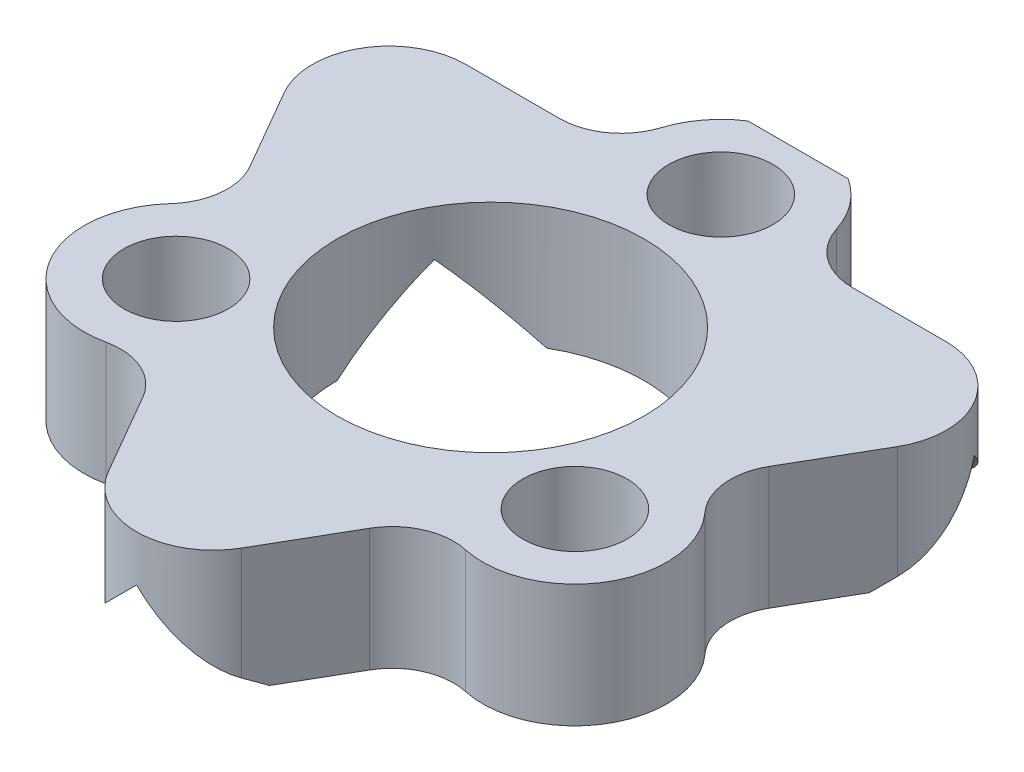
SolidWorks part; units mm, degrees
note: '?' marks a value the reader was unsure of.
material "Chrome Stainless Steel"
ref_plane "Front Plane" through (0, 0, 0) normal (0, 0, 1) x (1, 0, 0)
ref_plane "Top Plane" through (0, 0, 0) normal (0, 1, 0) x (1, 0, 0)
ref_plane "Right Plane" through (0, 0, 0) normal (1, 0, 0) x (0, 0, -1)
sketch "Sketch1" plane through (0, 0, 0) normal (0, 1, 0) x (1, 0, 0)
  line L0 (-9.9899, 3.147) -> (-8.4595, 0.4962)
  line L1 (2.1651, -10.4061) -> (3.6955, -7.7554)
  line L2 (7.8249, 6.897) -> (4.7641, 6.897)
  line L3 (-6.6271, -3.9469) -> (9.3066, 5.2524) construction
  line L4 (0, 6.897) -> (0, -11.9869) construction
  line L5 (4.3301, -2.6207) -> (-9.863, 5.5736) construction
  line L6 (-3.6955, -7.7554) -> (-2.1651, -10.4061)
  line L7 (-12.155, 6.897) -> (-2.961, 6.897) construction
  line L8 (12.155, 6.897) -> (0, -14.1561) construction
  line L9 (0, -14.1561) -> (-12.155, 6.897) construction
  line L10 (-12.155, 6.897) -> (12.155, 6.897) construction
  line L11 (8.4595, 0.4962) -> (9.9899, 3.147)
  line L12 (-4.7641, 6.897) -> (-7.8249, 6.897)
  line L13 (2.961, 6.897) -> (12.155, 6.897) construction
  circle A0 centre (0, -0.1207) radius 5
  circle A1 centre (0, -0.1207) radius 7.5 construction
  arc A2 (-5.8546, -6.8015) -> (-8.713, -1.8505) centre (-6.4952, -3.8707) cw
  arc A3 (-3.6955, -7.7554) -> (-5.8546, -6.8015) centre (-5.4275, -8.7554) ccw
  arc A4 (-9.9899, 3.147) -> (-7.8249, 6.897) centre (-7.8249, 4.397) cw
  arc A5 (2.1651, -10.4061) -> (-2.1651, -10.4061) centre (0, -9.1561) cw
  arc A6 (7.8249, 6.897) -> (9.9899, 3.147) centre (7.8249, 4.397) cw
  arc A7 (-8.4595, 0.4962) -> (-8.713, -1.8505) centre (-10.1916, -0.5038) cw
  arc A8 (3.6955, -7.7554) -> (5.8546, -6.8015) centre (5.4275, -8.7554) cw
  arc A9 (8.713, -1.8505) -> (5.8546, -6.8015) centre (6.4952, -3.8707) cw
  arc A10 (8.713, -1.8505) -> (8.4595, 0.4962) centre (10.1916, -0.5038) cw
  arc A11 (-2.8585, 8.2899) -> (2.8585, 8.2899) centre (0, 7.3793) cw
  arc A12 (-4.7641, 6.897) -> (-2.8585, 8.2899) centre (-4.7641, 8.897) ccw
  arc A13 (4.7641, 6.897) -> (2.8585, 8.2899) centre (4.7641, 8.897) cw
  point P7 (-6.4952, -3.8707)
  point P8 (0, 7.3793)
  point P9 (-12.155, 6.897)
  point P10 (6.4952, -3.8707)
  point P12 (0, -14.1561)
  point P16 (0, -0.1207)
  point P30 (-4.597, -6.1939)
  point P54 (40.5117, -0.4369)
  dimension "D1" = 10
  dimension "D5" = 15
  dimension "D6" = 2.5
  dimension "D7" = 3
  dimension "D8" = 2
  dimension "D9" = 2
  dimension "D10" = 3
  dimension "D11" = 2
  dimension "D12" = 3
  dimension "D2" = 120
  dimension "D3" = 240
  dimension "D4" = 24.31
  dimension "D13" = 0
extrude "Extrude1" add sketch "Sketch1" along normal blind 4
hole_wizard "M3 Clearance Hole1" positions "3DSketch1" profile "Sketch6" hole size "M3" standard "Ansi Metric"
sketch3d "3DSketch1"
  line L0 (-6.4952, 4, 3.8707) -> (-6.4952, 0, 3.8707) construction
  point P0 (-6.4952, 4, 3.8707)
sketch "Sketch6" plane through (-6.4952, 4, 3.8707) normal (1, 0, 0) x (0, 0, 1)
  line L0 (0, 0) -> (0, 11.0215)
  line L1 (0, 11.0215) -> (1.7, 10)
  line L2 (1.7, 10) -> (1.7, 0)
  line L5 (1.7, 0) -> (0, 0)
  line L10 (0, 11.0215) -> (-1.7, 10) construction
  line L11 (0, -6.35) -> (0, 107.95) construction
  dimension "Hole Dia." = 3.4
  dimension "Hole Depth" = 10
  dimension "Drill Angle" = 118
pattern_circular "CirPattern2" count 3 over 360 about axis through (0, 0, 0.1207) along (0, 1, 0) of "M3 Clearance Hole1"
sketch "GrooveSketch" plane through (0, 0, 0) normal (0, 0, 1) x (1, 0, 0)
  line L0 (-2.1651, 4) -> (2.1651, 0) construction
  line L1 (2.1651, 4) -> (-2.1651, 0) construction
  line L2 (0, 0) -> (0, 2.5) construction
  line L3 (-2.1651, 0) -> (2.1651, 0) construction
  line L4 (0, 0) -> (-5.8546, 0) construction
  line L5 (0, 0) -> (5.8546, 0) construction
  line L6 (0, 2.5) -> (-2.5, 0)
  line L7 (0, 2.5) -> (2.5, 0)
  circle A0 centre (0, -0.8658) radius 2.38 construction
  dimension "D2" = 4.76
  dimension "D1" = 2.5
  dimension "D3" = 90
  dimension "D4" = 45
extrude "Extrude4" cut sketch "GrooveSketch" along normal up to next from surface
ref_axis "Axis1" through (0, 4, 0.1207) along (0, -1, 0)?
ref_plane "Plane1" through (0.0523, 0, 0.0302) normal (-0.866, 0, -0.5) x (-0.5, 0, 0.866)
ref_plane "Plane2" through (-0.0523, 0, 0.0302) normal (0.866, 0, -0.5) x (-0.5, 0, -0.866)
sketch "Sketch9" plane through (0.0523, 0, 0.0302) normal (-0.866, 0, -0.5) x (-0.5, 0, 0.866)
  line L2 (0.1046, 0) -> (0.1046, 2.5) construction
  line L3 (0.1046, 0) -> (-8.7995, 0) construction
  line L4 (0.1046, 0) -> (2.9096, 0) construction
  line L5 (0.1046, 2.5) -> (-2.3954, 0)
  line L6 (0.1046, 2.5) -> (2.6046, 0)
  line L7 (0.1046, 4) -> (0.1046, 0) construction
  line L8 (-2.0605, 0) -> (2.2696, 0) construction
  circle A0 centre (0.1046, -0.8658) radius 2.38 construction
  dimension "D1" = 4.76
  dimension "D2" = 2.5
  dimension "D3" = 90
  dimension "D4" = 45
extrude "Extrude5" cut sketch "Sketch9" along normal through all from surface
sketch "Sketch10" plane through (-0.0523, 0, 0.0302) normal (0.866, 0, -0.5) x (-0.5, 0, -0.866)
  line L2 (-0.1046, 0) -> (-0.1046, 2.5) construction
  line L3 (-0.1046, 0) -> (13.4676, 0) construction
  line L4 (-0.1046, 0) -> (25.1768, 0) construction
  line L5 (-0.1046, 2.5) -> (-2.6046, 0)
  line L6 (-0.1046, 2.5) -> (2.3954, 0)
  line L7 (-2.2696, 0) -> (2.0605, 0) construction
  line L8 (-0.1046, 4) -> (-0.1046, 0) construction
  circle A0 centre (-0.1046, -0.8658) radius 2.38 construction
  dimension "D1" = 4.76
  dimension "D2" = 2.5
  dimension "D3" = 90
  dimension "D4" = 45
extrude "Extrude6" cut sketch "Sketch10" along normal through all from surface
sketch "Sketch11" plane through (0, 4, 0) normal (0, 1, 0) x (-1, 0, 0)
  line L0 (4.7641, -6.897) -> (7.8249, -6.897) construction
  line L1 (7.2757, -9.897) -> (-7.6674, -9.897)
  line L2 (7.2757, -9.897) -> (7.2757, -12.0797)
  line L3 (7.2757, -12.0797) -> (-7.6674, -12.0797)
  line L4 (-7.6674, -9.897) -> (-7.6674, -12.0797)
  point P4 (6.2945, -6.897)
  dimension "D1" = 3
extrude "Extrude7" cut sketch "Sketch11" against normal blind 10
sketch "Sketch13" plane through (0, 0, -9.897) normal (0, 0, -1) x (-1, 0, 0)
  line L0 (0, 7.9021) -> (0, -2.2272) construction
  line L1 (0, 4) -> (0, 0) construction
hole_wizard "Ø0.5 (0.5) Diameter Hole1" positions "3DSketch2" profile "Sketch14" hole size "Ø0.5" standard "Ansi Metric"
sketch3d "3DSketch2"
  line L0 (0, 7.9021, -9.897) -> (0, -2.2272, -9.897) construction
  line L1 (-1.6313, 4, -9.897) -> (1.6313, 4, -9.897) construction
  point P0 (0, 2.5, -9.897)
  dimension "D1" = 1.5
sketch "Sketch14" plane through (0, 2.5, -9.897) normal (1, 0, 0) x (0, 1, 0)
  line L0 (0, 0) -> (0, 0.4002)
  line L1 (0, 0.4002) -> (0.25, 0.25)
  line L2 (0.25, 0.25) -> (0.25, 0)
  line L5 (0.25, 0) -> (0, 0)
  line L10 (0, 0.4002) -> (-0.25, 0.25) construction
  line L11 (0, -6.35) -> (0, 107.95) construction
  dimension "Hole Dia." = 0.5
  dimension "Hole Depth" = 0.25
  dimension "Drill Angle" = 118
sketch "Sketch16" plane through (0, 0, -6.897) normal (0, 0, -1) x (-1, 0, 0)
  line L0 (0, -2.4425) -> (0, 8.6057) construction
hole_wizard "Ø0.5 (0.5) Diameter Hole2" positions "3DSketch4" profile "Sketch17" hole size "Ø0.5" standard "Ansi Metric"
sketch3d "3DSketch4"
  line L0 (7.8249, 4, -6.897) -> (4.7641, 4, -6.897) construction
  line L1 (0, -2.4425, -6.897) -> (0, 8.6057, -6.897) construction
  point P0 (6.5, 2.5, -6.897)
  dimension "D1" = 1.5
  dimension "D2" = 6.5
sketch "Sketch17" plane through (6.5, 2.5, -6.897) normal (1, 0, 0) x (0, 1, 0)
  line L0 (0, 0) -> (0, 0.4002)
  line L1 (0, 0.4002) -> (0.25, 0.25)
  line L2 (0.25, 0.25) -> (0.25, 0)
  line L5 (0.25, 0) -> (0, 0)
  line L10 (0, 0.4002) -> (-0.25, 0.25) construction
  line L11 (0, -6.35) -> (0, 107.95) construction
  dimension "Hole Dia." = 0.5
  dimension "Hole Depth" = 0.25
  dimension "Drill Angle" = 118
hole_wizard "Ø0.5 (0.5) Diameter Hole3" positions "3DSketch5" profile "Sketch18" hole size "Ø0.5" standard "Ansi Metric"
sketch3d "3DSketch5"
  line L0 (-4.7641, 4, -6.897) -> (-7.8249, 4, -6.897) construction
  line L1 (0, -2.4425, -6.897) -> (0, 8.6057, -6.897) construction
  point P0 (-6.5, 2.5, -6.897)
  dimension "D1" = 1.5
  dimension "D2" = 6.5
sketch "Sketch18" plane through (-6.5, 2.5, -6.897) normal (1, 0, 0) x (0, 1, 0)
  line L0 (0, 0) -> (0, 0.4002)
  line L1 (0, 0.4002) -> (0.25, 0.25)
  line L2 (0.25, 0.25) -> (0.25, 0)
  line L5 (0.25, 0) -> (0, 0)
  line L10 (0, 0.4002) -> (-0.25, 0.25) construction
  line L11 (0, -6.35) -> (0, 107.95) construction
  dimension "Hole Dia." = 0.5
  dimension "Hole Depth" = 0.25
  dimension "Drill Angle" = 118
